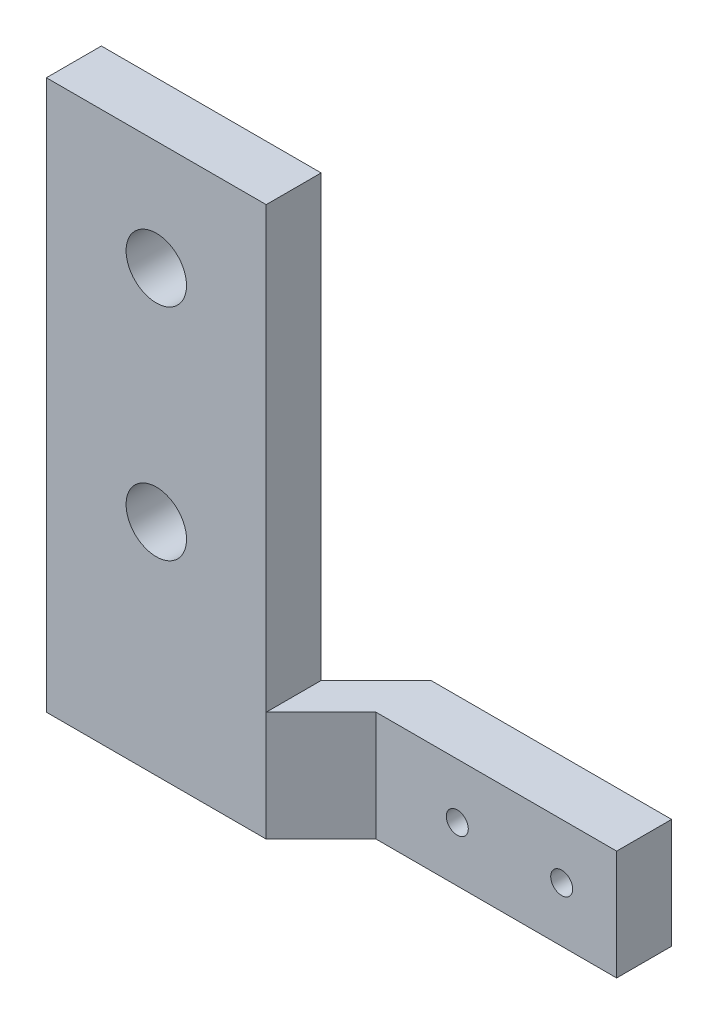
SolidWorks part; units mm, degrees
ref_plane "Plan de face" through (0, 0, 0) normal (0, 0, 1) x (1, 0, 0)
ref_plane "Plan de dessus" through (0, 0, 0) normal (0, 1, 0) x (1, 0, 0)
ref_plane "Plan de droite" through (0, 0, 0) normal (1, 0, 0) x (0, 0, -1)
sketch "Esquisse1" plane through (0, 0, 0) normal (0, 0, 1) x (1, 0, 0)
  line L0 (-27.8251, 16.7177) -> (-27.8251, -3.2823) construction
  line L2 (-37.8251, 26.7177) -> (-37.8251, -23.2823)
  line L8 (-37.8251, 26.7177) -> (-17.8251, 26.7177)
  line L9 (-17.8251, 26.7177) -> (-17.8251, -23.2823)
  line L12 (-37.8251, -23.2823) -> (-17.8251, -23.2823)
  circle A0 centre (-27.8251, 16.7177) radius 2.75
  circle A1 centre (-27.8251, -3.2823) radius 2.75
  point P17 (-27.8251, 26.7177)
  dimension "D3" = 5.5
  dimension "D1" = 20
  dimension "D2" = 50
  dimension "D4" = 10
  dimension "D5" = 20
extrude "Boss.-Extru.1" add sketch "Esquisse1" along normal blind 5
sketch "Esquisse2" plane through (0, -23.2823, 0) normal (0, -1, 0) x (1, 0, 0)
  line L0 (-17.8251, 0) -> (-17.8251, 5)
  line L1 (-17.8251, 5) -> (-12.8251, 0)
  line L2 (-12.8251, 0) -> (9.0631, 0)
  line L3 (9.0631, 0) -> (9.0631, -5)
  line L4 (9.0631, -5) -> (-12.8251, -5)
  line L5 (-12.8251, -5) -> (-17.8251, 0)
  dimension "D1" = 45
  dimension "D2" = 5
  dimension "D3" = 5
extrude "Boss.-Extru.2" add sketch "Esquisse2" against normal blind 10
sketch "Esquisse3" plane through (0, 0, 0) normal (0, 0, 1) x (1, 0, 0)
  line L0 (4.0631, -18.2823) -> (-5.4369, -18.2823) construction
  line L1 (9.0631, -13.2823) -> (9.0631, -23.2823) construction
  line L2 (9.0631, -13.2823) -> (-12.8251, -13.2823) construction
  circle A0 centre (4.0631, -18.2823) radius 1
  circle A1 centre (-5.4369, -18.2823) radius 1
  dimension "D4" = 2
  dimension "D1" = 9.5
  dimension "D2" = 5
  dimension "D3" = 5
extrude "Enlèv. mat.-Extru.1" cut sketch "Esquisse3" against normal up to next
